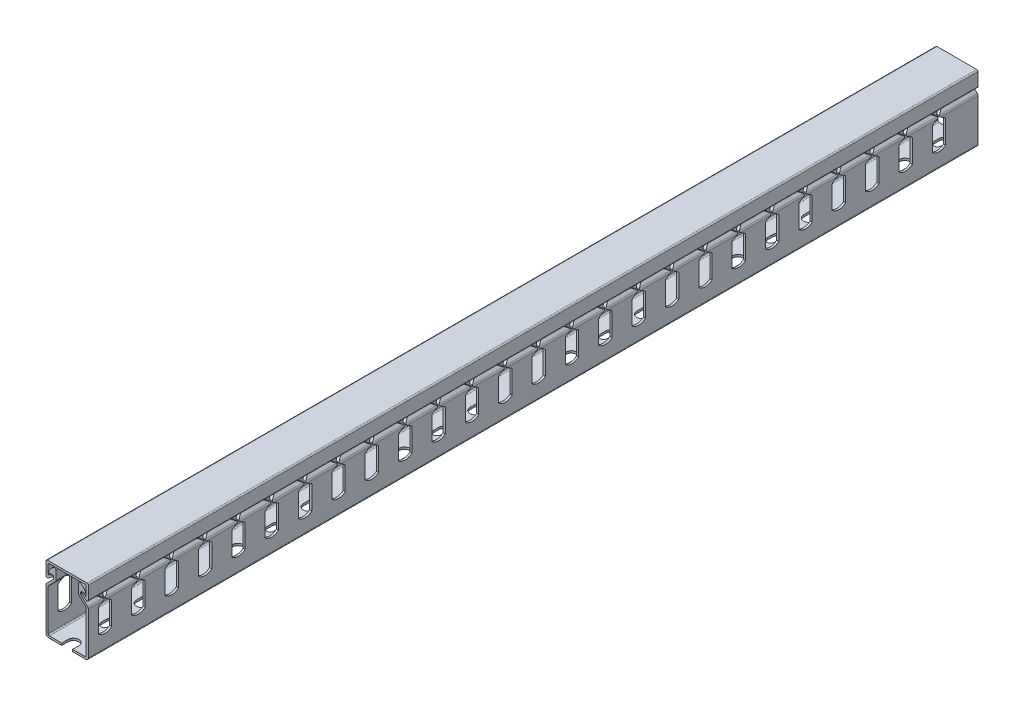
SolidWorks part; units mm, degrees
ref_plane "Front Plane" through (0, 0, 0) normal (0, 0, 1) x (1, 0, 0)
ref_plane "Top Plane" through (0, 0, 0) normal (0, 1, 0) x (1, 0, 0)
ref_plane "Right Plane" through (0, 0, 0) normal (1, 0, 0) x (0, 0, -1)
sketch "Sketch1" plane through (0, 0, 0) normal (0, 0, 1) x (1, 0, 0)
  line L0 (-12.7, 10.6985) -> (12.7, 10.6985) construction
  line L1 (12.7, -20) -> (-12.7, -20) construction
  line L2 (12.7, -20) -> (12.7, 20) construction
  line L3 (12.7, 20) -> (-12.7, 20) construction
  line L4 (-12.7, -20) -> (-12.7, 20) construction
  line L5 (0, 20) -> (0, -20) construction
  line L6 (12.7, 0) -> (-12.7, 0) construction
  line L7 (-12.7, 13.7872) -> (12.7, 13.7872) construction
  line L8 (6.8085, 20) -> (6.8085, 10.6985) construction
  line L9 (-6.8085, 20) -> (6.8085, 10.6985) construction
  line L10 (-6.8085, 20) -> (-6.8085, 10.6985) construction
  line L11 (-12.7, 18.222) -> (12.7, 18.222) construction
  line L12 (-12.7, 13.6284) -> (12.7, 13.6284) construction
  line L13 (-11.4341, 10.8542) -> (-7.685, 13.6284) construction
  line L14 (-10.1877, 13.798) -> (-6.8085, 14.3635) construction
  line L15 (12.7, 7.4) -> (6.8085, 13.4162) construction
  circle A0 centre (-11.9062, 11.4923) radius 0.7938 construction
  circle A1 centre (-10.3187, 14.5809) radius 0.7937 construction
  circle A2 centre (-7.6022, 17.4283) radius 0.7938 construction
  arc A3 (-7.9835, 18.1244) -> (-11.0321, 14.929) centre (-4.4831, 11.7329) ccw construction
  point P0 (0, 0)
  point P4 (11.43, 0)
  point P13 (0, 15.3493)
  point P16 (-11.1125, 13.7872)
  point P21 (-11.1125, 11.4923)
  point P26 (-10.3188, 13.7872)
  point P27 (-10.3188, 13.7872)
  point P28 (-11.1125, 14.5809)
  point P36 (12.7, 7.4)
  dimension "D6" = 7.2873
  dimension "Width" = 25.4
  dimension "Heigth" = 40
  dimension "Wall Thickness" = 1.27
  dimension "Cap Height" = 9.3015
  dimension "Lip Height" = 6.2128
  dimension "D1" = 13.6169
  dimension "D2" = 1.778
  dimension "Lip From Edge" = 1.5875
  dimension "D4" = 0.1588
  dimension "D5" = 36.5
  dimension "D3" = 80.5
  dimension "Shoulder Height" = 27.4
  dimension "D7" = 44.4
sketch "Sketch3" plane through (0, 0, 0) normal (1, 0, 0) x (0, 0, -1)
  line L0 (266.7, 0) -> (-266.7, 0) construction
  line L1 (-266.7, 20) -> (-266.7, -20) construction
  line L2 (-266.7, -20) -> (266.7, -20) construction
  line L3 (266.7, -20) -> (266.7, 20) construction
  line L4 (266.7, 20) -> (-266.7, 20) construction
  line L5 (-252.7, 20) -> (-252.7, 9.8437) construction
  line L6 (-252.7, 9.8437) -> (-256.573, 7.4) construction
  line L7 (-256.573, 7.4) -> (-256.827, 7.4) construction
  line L8 (-256.827, 7.4) -> (-260.7, 9.8437) construction
  line L9 (-260.7, 9.8437) -> (-260.7, 20) construction
  line L10 (-256.827, 7.4) -> (-260.7, 4.9563) construction
  line L11 (-260.7, 4.9563) -> (-260.7, -9.1796) construction
  line L12 (-260.7, -9.1796) -> (-252.7, -9.1796) construction
  line L13 (-252.7, -9.1796) -> (-252.7, 4.9563) construction
  line L14 (-256.573, 7.4) -> (-252.7, 4.9563) construction
  line L15 (-256.7, 7.4) -> (-256.7, -9.1796) construction
  line L16 (-256.7, 7.4) -> (-256.7, 20) construction
  line L17 (-260.7, 4.9563) -> (-252.7, 4.9563) construction
  line L18 (0, 7.4) -> (-256.573, 7.4) construction
  line L19 (-260.7, 9.8437) -> (-260.7, 4.9563) construction
  line L20 (-256.827, 7.4) -> (-260.7, 7.4) construction
  line L21 (-252.7, 4.9563) -> (-240.7, 4.9563) construction
  line L22 (-240.7, 4.9563) -> (-232.7, 4.9563) construction
  line L23 (-236.7, 4.9563) -> (-236.7, -9.1796) construction
  line L24 (-139.7, 20) -> (-139.7, -20) construction
  line L25 (139.7, 20) -> (139.7, -20) construction
  arc A0 (-260.7, -9.1796) -> (-252.7, -9.1796) centre (-256.7, -4.7075) ccw construction
  circle A1 centre (-257.5707, 7.4) radius 0.3969 construction
  circle A2 centre (-255.8293, 7.4) radius 0.3969 construction
  point P29 (-232.7, 4.9563)
  point P30 (-240.7, 4.9563)
  point P31 (-240.7, 4.9563)
  point P32 (-236.7, 4.9563)
  point P34 (-139.7, 0)
  point P39 (139.7, 0)
  dimension "D2" = 6
  dimension "D6" = 0.7937
  dimension "Length" = 533.4
  dimension "Side Cut Out Width" = 8
  dimension "D3" = 6
  dimension "D1" = 10.8204
  dimension "D4" = 64.5
  dimension "D5" = 0.254
  dimension "Cut Spacing" = 12
  dimension "Cut Center To Center" = 20
  dimension "D7" = 127
  dimension "D8" = 127
sketch "Sketch4" plane through (0, 0, 0) normal (0, 1, 0) x (1, 0, 0)
  line L0 (0, -270.45) -> (0, -262.95) construction
  line L1 (-12.7, 266.7) -> (12.7, 266.7) construction
  line L2 (-12.7, 266.7) -> (-12.7, -266.7) construction
  line L3 (-12.7, -266.7) -> (12.7, -266.7) construction
  line L4 (12.7, 266.7) -> (12.7, -266.7) construction
  line L5 (0, -266.7) -> (0, 266.7) construction
  line L6 (-12.7, 0) -> (12.7, 0) construction
  line L7 (-3.25, -270.45) -> (-3.25, -262.95) construction
  line L8 (3.25, -270.45) -> (3.25, -262.95) construction
  line L9 (0, -244.2) -> (0, -240.7) construction
  line L10 (-2.25, -244.2) -> (-2.25, -240.7) construction
  line L11 (2.25, -244.2) -> (2.25, -240.7) construction
  line L12 (0, -221.95) -> (0, -214.45) construction
  line L13 (-3.25, -221.95) -> (-3.25, -214.45) construction
  line L14 (3.25, -221.95) -> (3.25, -214.45) construction
  line L15 (0, -191.45) -> (0, -194.95) construction
  line L16 (2.25, -191.45) -> (2.25, -194.95) construction
  line L17 (-2.25, -191.45) -> (-2.25, -194.95) construction
  line L18 (-12.7, -139.7) -> (12.7, -139.7) construction
  line L19 (-12.7, 139.7) -> (12.7, 139.7) construction
  arc A0 (-3.25, -270.45) -> (3.25, -270.45) centre (0, -270.45) ccw construction
  arc A1 (3.25, -262.95) -> (-3.25, -262.95) centre (0, -262.95) ccw construction
  arc A2 (-2.25, -244.2) -> (2.25, -244.2) centre (0, -244.2) ccw construction
  arc A3 (2.25, -240.7) -> (-2.25, -240.7) centre (0, -240.7) ccw construction
  arc A4 (-3.25, -221.95) -> (3.25, -221.95) centre (0, -221.95) ccw construction
  arc A5 (3.25, -214.45) -> (-3.25, -214.45) centre (0, -214.45) ccw construction
  arc A6 (2.25, -191.45) -> (-2.25, -191.45) centre (0, -191.45) ccw construction
  arc A7 (-2.25, -194.95) -> (2.25, -194.95) centre (0, -194.95) ccw construction
  point P0 (0, 0)
  point P5 (0, -266.7)
  point P13 (0, -242.45)
  point P18 (0, -238.45)
  point P19 (0, -246.45)
  point P20 (0, -259.7)
  point P21 (0, -273.7)
  point P24 (0, -218.2)
  point P31 (0, -193.2)
  point P40 (0, -225.2)
  point P41 (0, -211.2)
  dimension "Large Hole Radius" = 3.25
  dimension "Large Hole Length" = 14
  dimension "Slot With" = 8
  dimension "End Hole Spacing" = 48.5
  dimension "D4" = 24.25
  dimension "Hole Spacing" = 25
  dimension "Mounting Hole Diameter" = 4.5
sketch "Sketch5" plane through (0, 0, 0) normal (0, 0, 1) x (1, 0, 0)
  line L0 (-6.8085, 17.4283) -> (-6.8085, 11.6011)
  line L1 (-6.8085, 20) -> (-6.8085, 10.6985) construction
  line L2 (-6.8085, 11.6011) -> (-11.43, 6.8817)
  line L3 (-11.43, 6.8817) -> (-11.43, -18.73)
  line L4 (-11.43, -18.73) -> (11.43, -18.73)
  line L5 (11.43, -18.73) -> (11.43, 6.8817)
  line L6 (11.43, 6.8817) -> (6.8085, 11.6011)
  line L7 (6.8085, 11.6011) -> (6.8085, 17.4283)
  line L8 (6.8085, 20) -> (6.8085, 10.6985) construction
  line L9 (12.7, 7.4) -> (6.8085, 13.4162) construction
  line L10 (0, 20) -> (0, -20) construction
  line L11 (11.43, 0) -> (12.7, 0) construction
  line L12 (8.0785, 12.1194) -> (6.8085, 12.1194) construction
  line L13 (-10.1877, 13.798) -> (-6.8085, 14.3635) construction
  line L14 (-10.1877, 13.798) -> (-8.0785, 14.151)
  line L15 (-8.0785, 14.151) -> (-8.0785, 12.1194)
  line L16 (-8.0785, 12.1194) -> (-12.7, 7.4)
  line L17 (-12.7, -20) -> (-12.7, 20) construction
  line L18 (-12.7, 7.4) -> (-12.7, -20)
  line L19 (-12.7, -20) -> (12.7, -20)
  line L20 (12.7, -20) -> (12.7, 7.4)
  line L21 (12.7, 7.4) -> (8.0785, 12.1194)
  line L22 (8.0785, 12.1194) -> (8.0785, 14.151)
  line L23 (6.8085, 12.1194) -> (-6.8085, 12.1194) construction
  line L24 (-6.8085, 12.1194) -> (-8.0785, 12.1194) construction
  line L25 (11.43, 6.8817) -> (12.3374, 7.7703) construction
  line L26 (-12.7, 18.222) -> (12.7, 18.222) construction
  line L27 (10.1877, 13.798) -> (8.0785, 14.151)
  line L28 (11.43, -18.73) -> (11.43, -20) construction
  line L29 (-12.7, 20) -> (-12.7, 11.4923)
  line L30 (-12.7, 20) -> (12.7, 20)
  line L31 (-11.4341, 10.8542) -> (-8.7512, 12.8395)
  line L32 (-11.4341, 10.8542) -> (-7.685, 13.6284) construction
  line L33 (12.7, 20) -> (12.7, 11.4923)
  line L34 (12.7, -20) -> (12.7, 20) construction
  line L35 (8.7512, 12.8395) -> (11.4341, 10.8542)
  line L36 (-12.7, 10.6985) -> (12.7, 10.6985) construction
  line L37 (-11.43, 12.4371) -> (-11.43, 18.73)
  line L38 (-11.43, 18.73) -> (11.43, 18.73)
  line L39 (11.43, 18.73) -> (11.43, 12.4371)
  line L40 (-11.43, 18.73) -> (-11.43, 20) construction
  line L41 (-11.43, 18.73) -> (-12.7, 18.73) construction
  line L42 (-11.43, 12.4371) -> (-10.6707, 12.999)
  line L43 (-11.0503, 12.7181) -> (-10.2949, 11.6972) construction
  line L44 (-8.9869, 13.5542) -> (-8.9869, 13.158) construction
  line L45 (10.6707, 12.999) -> (11.43, 12.4371)
  line L46 (10.6707, 12.999) -> (9.9153, 11.9781) construction
  circle A0 centre (-7.6022, 17.4283) radius 0.7938 construction
  arc A1 (-7.9835, 18.1244) -> (-11.0321, 14.929) centre (-4.4831, 11.7329) ccw construction
  arc A2 (-7.9835, 18.1244) -> (-11.0321, 14.929) centre (-4.4831, 11.7329) ccw
  circle A3 centre (-10.3187, 14.5809) radius 0.7937 construction
  arc A4 (-11.0321, 14.929) -> (-10.1877, 13.798) centre (-10.3187, 14.5809) ccw
  arc A5 (-6.8085, 17.4283) -> (-7.9835, 18.1244) centre (-7.6022, 17.4283) ccw
  arc A6 (7.9835, 18.1244) -> (6.8085, 17.4283) centre (7.6022, 17.4282) ccw
  arc A7 (10.1877, 13.798) -> (11.0321, 14.929) centre (10.3187, 14.5809) ccw
  arc A8 (7.9835, 18.1244) -> (11.0321, 14.929) centre (4.4831, 11.7329) cw
  circle A9 centre (-11.9062, 11.4923) radius 0.7938 construction
  arc A10 (-12.7, 11.4923) -> (-11.4341, 10.8542) centre (-11.9062, 11.4923) ccw
  arc A11 (11.4341, 10.8542) -> (12.7, 11.4923) centre (11.9062, 11.4923) ccw
  arc A12 (-8.7512, 12.8395) -> (-8.9869, 13.5542) centre (-8.9869, 13.158) ccw
  arc A13 (-10.6707, 12.999) -> (-8.9869, 13.5542) centre (-8.9869, 10.7234) cw
  arc A14 (8.7512, 12.8395) -> (8.9869, 13.5542) centre (8.9869, 13.158) cw
  arc A15 (8.9869, 13.5542) -> (10.6707, 12.999) centre (8.9869, 10.7234) cw
  point P10 (0, -18.73)
  point P81 (0, 18.73)
  dimension "D2" = 0.3962
  dimension "D1" = 3.3376
extrude "Boss-Extrude1" add sketch "Sketch5" along normal up to vertex (266.7 mm away) and the other way up to vertex (266.7 mm away) up to point (0, -20, 266.7) other way up to point (0, -20, -266.7)
fillet "Fillet1" radius 0.254 2 edges at (-11.43, 12.4371, 0) (11.43, 12.4371, 0)
fillet "Fillet2" radius 0.7937 4 edges at (12.7, 20, 0) (11.43, 18.73, 0) (-11.43, 18.73, 0) (-12.7, 20, 0)
fillet "Fillet3" radius 1.5875 4 edges at (-12.7, -20, 0) (12.7, -20, 0) (12.7, 7.4, 0) (-12.7, 7.4, 0)
fillet "Fillet4" radius 0.7937 8 edges at (-11.43, -18.73, 0) (11.43, -18.73, 0) (8.0785, 14.151, 0) (-8.0785, 14.151, 0) (-11.43, 6.8817, 0) (-6.8085, 11.6011, 0) (6.8085, 11.6011, 0) (11.43, 6.8817, 0)
sketch "Sketch6" plane through (0, 0, 0) normal (1, 0, 0) x (0, 0, -1)
  line L0 (-260.7, 20) -> (-260.7, 10.2814)
  line L1 (-260.7, 4.9563) -> (-260.7, -9.1796) construction
  line L2 (-256.827, 7.4) -> (-260.7, 4.9563) construction
  line L3 (-252.7, -9.1796) -> (-252.7, 4.9563) construction
  line L4 (-256.573, 7.4) -> (-252.7, 4.9563) construction
  line L5 (-252.7, 9.8437) -> (-256.573, 7.4) construction
  line L6 (-252.7, 20) -> (-252.7, 9.8437) construction
  line L7 (-256.827, 7.4) -> (-260.7, 9.8437) construction
  line L8 (-260.7, 4.5186) -> (-260.7, -9.1796)
  line L9 (-257.359, 7.0644) -> (-260.3298, 5.1899)
  line L10 (-252.7, -9.1796) -> (-252.7, 4.5186)
  line L11 (-256.041, 7.0644) -> (-253.0702, 5.1899)
  line L12 (-253.0702, 9.6101) -> (-256.041, 7.7356)
  line L13 (-252.7, 20) -> (-252.7, 10.2814)
  line L14 (-257.359, 7.7356) -> (-260.3298, 9.6101)
  line L15 (-252.7, 20) -> (-260.7, 20)
  circle A0 centre (-255.8293, 7.4) radius 0.3969 construction
  circle A1 centre (-257.5707, 7.4) radius 0.3969 construction
  arc A2 (-256.041, 7.7356) -> (-256.041, 7.0644) centre (-255.8293, 7.4) ccw
  arc A3 (-257.359, 7.0644) -> (-257.359, 7.7356) centre (-257.5707, 7.4) ccw
  arc A4 (-260.7, -9.1796) -> (-252.7, -9.1796) centre (-256.7, -4.7075) ccw construction
  arc A5 (-260.7, -9.1796) -> (-252.7, -9.1796) centre (-256.7, -4.7075) ccw
  arc A6 (-253.0702, 9.6101) -> (-252.7, 10.2814) centre (-253.4937, 10.2814) ccw
  arc A7 (-252.7, 4.5186) -> (-253.0702, 5.1899) centre (-253.4937, 4.5186) ccw
  arc A8 (-260.7, 4.5186) -> (-260.3298, 5.1899) centre (-259.9062, 4.5186) cw
  arc A9 (-260.7, 10.2814) -> (-260.3298, 9.6101) centre (-259.9062, 10.2814) ccw
  dimension "D1" = 0.7937
extrude "Cut-Extrude2" cut sketch "Sketch6" against normal through all both and the other way through all
pattern_linear "LPattern2" count 26 spacing 20 along (0, 0, -1) of "Cut-Extrude2"
sketch "Sketch7" plane through (0, -20, 0) normal (0, -1, 0) x (1, 0, 0)
  line L0 (-3.25, 270.45) -> (-3.25, 262.95) construction
  line L1 (3.25, 270.45) -> (3.25, 262.95) construction
  line L2 (-3.25, 270.45) -> (-3.25, 262.95)
  line L3 (3.25, 270.45) -> (3.25, 262.95)
  line L4 (-2.25, 244.2) -> (-2.25, 240.7) construction
  line L5 (2.25, 244.2) -> (2.25, 240.7) construction
  line L6 (-2.25, 244.2) -> (-2.25, 240.7)
  line L7 (2.25, 244.2) -> (2.25, 240.7)
  arc A0 (3.25, 270.45) -> (-3.25, 270.45) centre (0, 270.45) ccw construction
  arc A1 (-3.25, 262.95) -> (3.25, 262.95) centre (0, 262.95) ccw construction
  arc A2 (3.25, 270.45) -> (-3.25, 270.45) centre (0, 270.45) ccw
  arc A3 (-3.25, 262.95) -> (3.25, 262.95) centre (0, 262.95) ccw
  arc A4 (2.25, 244.2) -> (-2.25, 244.2) centre (0, 244.2) ccw construction
  arc A5 (-2.25, 240.7) -> (2.25, 240.7) centre (0, 240.7) ccw construction
  arc A6 (2.25, 244.2) -> (-2.25, 244.2) centre (0, 244.2) ccw
  arc A7 (-2.25, 240.7) -> (2.25, 240.7) centre (0, 240.7) ccw
extrude "Cut-Extrude3" cut sketch "Sketch7" against normal up to vertex (1.27 mm away) up to point (10.6363, -18.73, 266.7)
sketch "Sketch8" plane through (0, -20, 0) normal (0, -1, 0) x (1, 0, 0)
  line L0 (-2.25, 191.45) -> (-2.25, 194.95) construction
  line L1 (2.25, 191.45) -> (2.25, 194.95) construction
  line L2 (3.25, 221.95) -> (3.25, 214.45) construction
  line L3 (-3.25, 221.95) -> (-3.25, 214.45) construction
  line L4 (-2.25, 191.45) -> (-2.25, 194.95)
  line L5 (2.25, 191.45) -> (2.25, 194.95)
  line L6 (3.25, 221.95) -> (3.25, 214.45)
  line L7 (-3.25, 221.95) -> (-3.25, 214.45)
  arc A0 (-2.25, 191.45) -> (2.25, 191.45) centre (0, 191.45) ccw construction
  arc A1 (2.25, 194.95) -> (-2.25, 194.95) centre (0, 194.95) ccw construction
  arc A2 (3.25, 221.95) -> (-3.25, 221.95) centre (0, 221.95) ccw construction
  arc A3 (-3.25, 214.45) -> (3.25, 214.45) centre (0, 214.45) ccw construction
  arc A4 (-2.25, 191.45) -> (2.25, 191.45) centre (0, 191.45) ccw
  arc A5 (2.25, 194.95) -> (-2.25, 194.95) centre (0, 194.95) ccw
  arc A6 (3.25, 221.95) -> (-3.25, 221.95) centre (0, 221.95) ccw
  arc A7 (-3.25, 214.45) -> (3.25, 214.45) centre (0, 214.45) ccw
extrude "Cut-Extrude4" cut sketch "Sketch8" against normal up to vertex (1.27 mm away) up to point (-3.25, -18.73, 266.7)
pattern_linear "LPattern3" count 12 spacing 50 along (0, 0, -1) of "Cut-Extrude4"
equation "\"D2@Sketch1\"=\"Wall Thickness@Sketch1\"*1.4"
equation "\"D4@Sketch1\"=\"Wall Thickness@Sketch1\"*.125"
equation "\"D2@Sketch3\" = \"Side Cut Out Width@Sketch3\" * .75"
equation "\"D4@Sketch4\" = \"End Hole Spacing@Sketch4\" / 2"
equation "\"D3@LPattern2\"=\"Cut Center To Center@Sketch3\""
equation "\"D1@LPattern2\"=\"Length@Sketch3\"/\"Cut Center To Center@Sketch3\"-1"
equation "\"D1@LPattern3\"=(\"Length@Sketch3\"/50mm)+1"
equation "\"D7@Sketch3\"=\"D8@Sketch3\""
